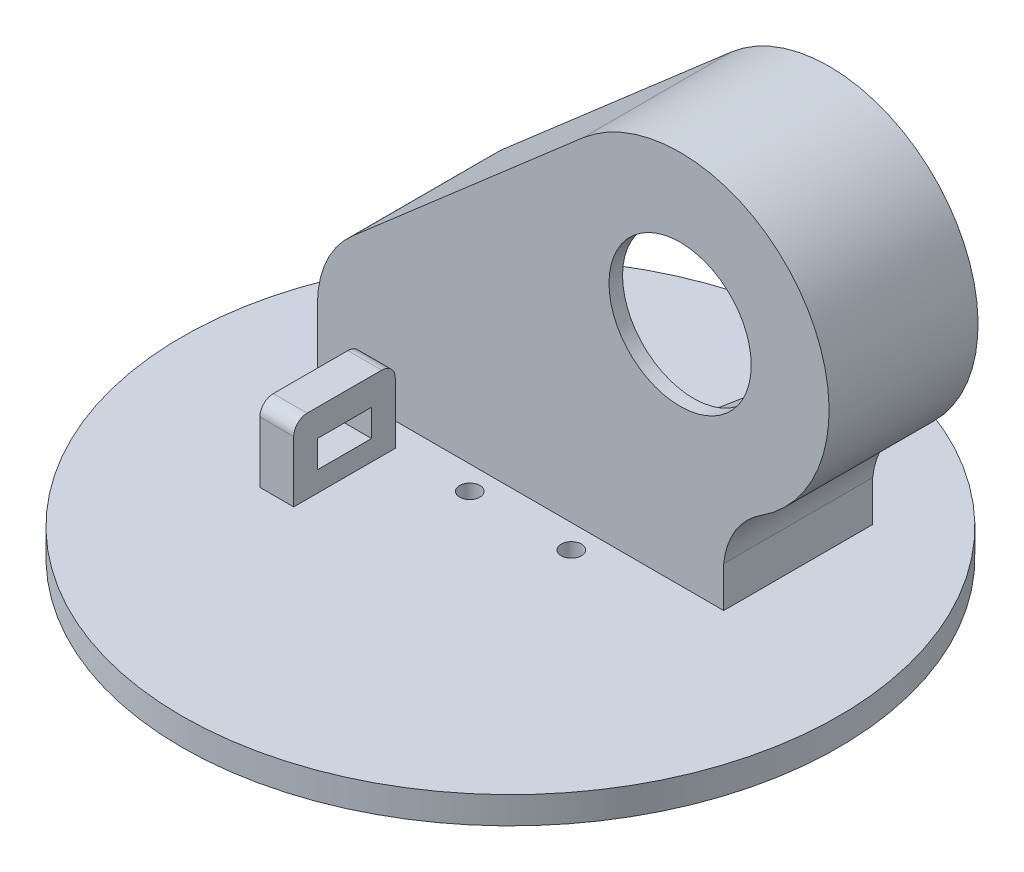
SolidWorks part; units mm, degrees
material "ABS"
ref_plane "Front Plane" through (0, 0, 0) normal (0, 0, 1) x (1, 0, 0)
ref_plane "Top Plane" through (0, 0, 0) normal (0, 1, 0) x (1, 0, 0)
ref_plane "Right Plane" through (0, 0, 0) normal (1, 0, 0) x (0, 0, -1)
sketch "Sketch1" plane through (0, 0, 0) normal (0, 1, 0) x (1, 0, 0)
  line L0 (-25.5, 4.5) -> (18.5, 4.5) construction
  line L1 (-33.5, 26.5) -> (-25.5, 26.5) construction
  line L2 (-33.5, 26.5) -> (-33.5, 4.5) construction
  line L3 (-33.5, 4.5) -> (-25.5, 4.5) construction
  line L4 (-25.5, 26.5) -> (-25.5, 4.5) construction
  line L5 (-33.5, 26.5) -> (-25.5, 4.5) construction
  line L6 (-33.5, 4.5) -> (-25.5, 26.5) construction
  line L7 (26.5, 26.5) -> (18.5, 26.5) construction
  line L8 (26.5, 26.5) -> (26.5, 4.5) construction
  line L9 (26.5, 4.5) -> (18.5, 4.5) construction
  line L10 (18.5, 26.5) -> (18.5, 4.5) construction
  line L11 (26.5, 26.5) -> (18.5, 4.5) construction
  line L12 (26.5, 4.5) -> (18.5, 26.5) construction
  line L13 (-7.5, 1.5) -> (7.5, 1.5) construction
  line L15 (-23.5, 1.5) -> (-18.5, 1.5)
  line L16 (-23.5, 1.5) -> (-23.5, -13.5)
  line L17 (-23.5, -13.5) -> (-18.5, -13.5)
  line L18 (-18.5, 1.5) -> (-18.5, -13.5)
  line L19 (-23.5, 1.5) -> (-18.5, -13.5) construction
  line L20 (-23.5, -13.5) -> (-18.5, 1.5) construction
  circle A0 centre (0, 0) radius 48.5
  circle A1 centre (7.5, 1.5) radius 1.5
  circle A2 centre (-7.5, 1.5) radius 1.5
  point P7 (-29.5, 15.5)
  point P12 (22.5, 15.5)
  point P13 (0, 48.5)
  point P14 (22.5, 26.5)
  point P19 (0, 1.5)
  point P20 (-48.5, 0)
  point P25 (-21, -6)
  dimension "D1" = 97
  dimension "D8" = 3
  dimension "D2" = 22
  dimension "D3" = 22
  dimension "D4" = 8
  dimension "D5" = 22
  dimension "D6" = 15
  dimension "D7" = 3
  dimension "D9" = 10
  dimension "D10" = 5
  dimension "D11" = 60
  dimension "D12" = 15
  dimension "D13" = 15
extrude "Boss-Extrude1" add sketch "Sketch1" along normal blind 4
extrude "Boss-Extrude2" add sketch "Sketch1<4>" along normal blind 15 contours L16 L17 L18 L15
sketch "Sketch1<4>" plane through (0, 0, 0) normal (0, 1, 0) x (1, 0, 0) same geometry as "Sketch1"
fillet "Fillet1" radius 2 2 edges at (-21, 15, -1.5) (-21, 15, 13.5)
ref_plane "Plane1" through (0, 0, -16) normal (0, 0, 1) x (1, 0, 0)
sketch "Sketch3" plane through (0, 0, -16) normal (0, 0, 1) x (1, 0, 0)
  line L0 (-33.5, 0) -> (-33.5, 13.1621)
  line L1 (-28.3384, 24.4849) -> (5.6302, 54)
  line L2 (26.5, 10) -> (26.5, 0)
  line L3 (48.5, 4) -> (-48.5, 4) construction
  line L4 (-33.5, 0) -> (26.5, 0)
  arc A0 (5.6302, 54) -> (31.952, 18.8844) centre (20.0598, 37.3932) cw
  arc A1 (31.952, 18.8844) -> (26.5, 10) centre (38.4387, 8.7887) ccw
  arc A2 (-33.5, 13.1621) -> (-28.3384, 24.4849) centre (-18.5, 13.1621) cw
  circle A3 centre (20.0598, 37.3932) radius 10.5
  point P12 (-33.5, 20)
  dimension "D2" = 15
  dimension "D5" = 22
  dimension "D6" = 12
  dimension "D8" = 21
  dimension "D1" = 20
  dimension "D3" = 45
  dimension "D4" = 50
  dimension "D7" = 60
  dimension "D9" = 10
extrude "Extrude-Thin1" add sketch "Sketch3" against normal mid plane 22 thin contours L0 A2 L1 A0 A1 L2 thin type one direction wall 10
extrude "Boss-Extrude3" add sketch "Sketch3<4>" along normal up to surface (11 mm away) up to face at (1.6233, 19.6589, -5)
sketch "Sketch3<4>" plane through (0, 0, -16) normal (0, 0, 1) x (1, 0, 0) same geometry as "Sketch3"
sketch "Sketch5" plane through (0, 0, -27) normal (0, 0, -1) x (-1, 0, 0)
  line L1 (-16.5, 4) -> (25.5, 4)
  line L8 (-16.5, 4) -> (-26.5, 4) construction
  line L9 (33.5, 4) -> (23.5, 4) construction
  line L11 (30.5, 4) -> (30.5, 13.1621)
  line L12 (26.3707, 22.2204) -> (-7.5978, 51.7354)
  line L13 (-23.5, 10.1433) -> (-23.5, 4)
  line L15 (12.8136, 34) -> (-7.5978, 51.7354)
  line L17 (48.5, 4) -> (-48.5, 4) construction
  line L18 (33.5, 4) -> (33.5, 13.1621) construction
  arc A15 (-30.3303, 21.4083) -> (-16.5, 4) centre (-48.9654, -7.5946) cw
  arc A16 (12.8136, 34) -> (25.5, 4) centre (-11.4751, 6.0464) cw
  arc A19 (30.5, 13.1621) -> (26.3707, 22.2204) centre (18.5, 13.1621) ccw
  arc A20 (-23.5, 10.1433) -> (-30.3303, 21.4083) centre (-38.4387, 8.7887) ccw
  arc A21 (-7.5978, 51.7354) -> (-30.3303, 21.4083) centre (-20.0598, 37.3932) ccw
  arc A24 (-7.5978, 51.7354) -> (-30.3303, 21.4083) centre (-20.0598, 37.3932) ccw
  dimension "D3" = 30
  dimension "D2" = 10
  dimension "D4" = 8
  dimension "D1" = 3
extrude "Cut-Extrude2" cut sketch "Sketch5" against normal blind 11
sketch "Sketch8" plane through (0, 0, -16) normal (0, 0, -1) x (-1, 0, 0)
  line L0 (-36.323, 36.6801) -> (-22.1816, 53.5331)
  line L1 (-36.323, 36.6801) -> (-4.1491, 9.6831)
  line L2 (-22.1816, 53.5331) -> (9.9922, 26.536)
  line L3 (-4.1491, 9.6831) -> (9.9922, 26.536)
  line L4 (-4.1491, 9.6831) -> (25.0827, 9.6831) construction
  line L5 (-34.7644, 43.2048) -> (-28.3365, 50.8652) construction
  line L6 (-20.236, 23.1816) -> (-6.0947, 40.0346) construction
  circle A0 centre (-34.7644, 43.2048) radius 1.5
  circle A1 centre (-28.3365, 50.8652) radius 1.5
  circle A2 centre (8.4337, 20.0114) radius 1.5
  circle A3 centre (2.0058, 12.351) radius 1.5
  point P0 (-20.0598, 37.3932)
  dimension "D6" = 3
  dimension "D2" = 42
  dimension "D3" = 22
  dimension "D4" = 11
  dimension "D5" = 15
  dimension "D7" = 6
  dimension "D8" = 10
  dimension "D9" = 6
  dimension "D10" = 3
  dimension "D11" = 50
  dimension "D12" = 12
extrude "Cut-Extrude3" cut sketch "Sketch8" against normal blind 9
sketch "Sketch9" plane through (-23.5, 0, 0) normal (-1, 0, 0) x (0, 0, 1)
  line L0 (-1.5, 13) -> (-1.5, 4) construction
  line L1 (2, 11) -> (10, 11)
  line L2 (2, 11) -> (2, 7)
  line L3 (2, 7) -> (10, 7)
  line L4 (10, 11) -> (10, 7)
  line L5 (2, 11) -> (10, 7) construction
  line L6 (2, 7) -> (10, 11) construction
  line L7 (13.5, 13) -> (13.5, 4) construction
  line L8 (0.5, 15) -> (11.5, 15) construction
  point P4 (6, 9)
  dimension "D1" = 8
  dimension "D2" = 3.5
  dimension "D3" = 3.5
  dimension "D4" = 4
  dimension "D5" = 4
extrude "Cut-Extrude4" cut sketch "Sketch9" against normal through all both and the other way through all
